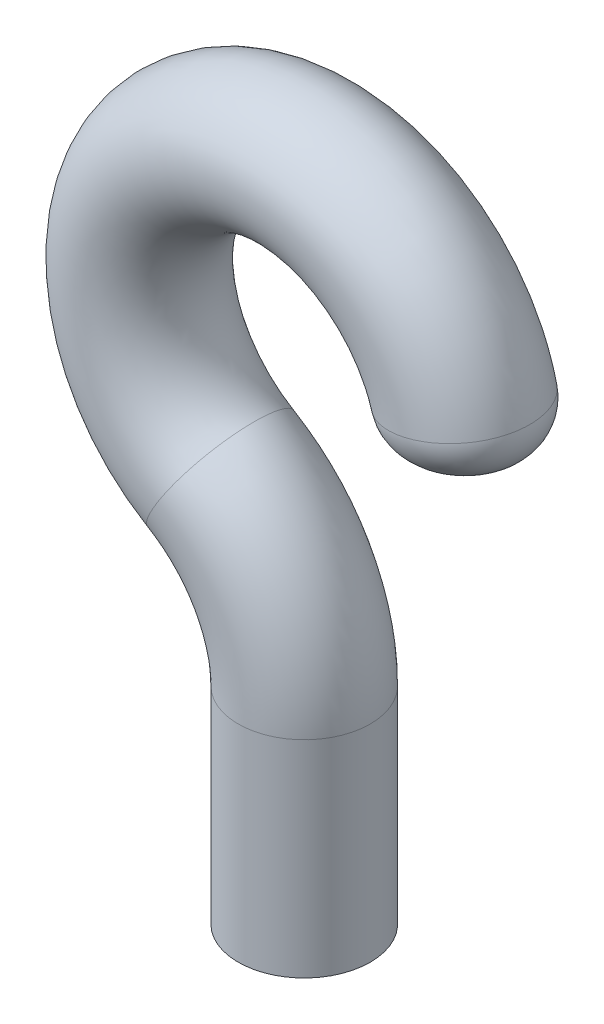
SolidWorks part; units mm, degrees
material "AISI 1020 Steel, Cold Rolled"
ref_plane "Front Plane" through (0, 0, 0) normal (0, 0, 1) x (1, 0, 0)
ref_plane "Top Plane" through (0, 0, 0) normal (0, 1, 0) x (1, 0, 0)
ref_plane "Right Plane" through (0, 0, 0) normal (1, 0, 0) x (0, 0, -1)
sketch "Sketch2" plane through (0, 0, 0) normal (0, 0, 1) x (1, 0, 0)
  line L0 (0, 0) -> (0, 25)
  arc A0 (0, 25) -> (-10.1538, 42.7692) centre (-20.625, 25) ccw
  arc A2 (20, 60) -> (-10.1538, 42.7692) centre (0, 60) ccw
  point P5 (15.6894, 39.9643)
  point P8 (0, 0)
  point P9 (-4.3447, 28.3953)
  point P10 (0, 0)
  point P11 (0, 0)
  dimension "D2" = 20
  dimension "D1" = 25
  dimension "D3" = 60
sweep "Sweep1" add path "Sketch2" circular profile diameter 16 parameters "D3"=16
cosmetic thread "Cosmetic Thread1" parameters "D2"=13.797
cosmetic thread "Cosmetic Thread2" parameters "D2"=13.797
fillet "Fillet1" radius 5 1 edges at (12, 60, 0)
